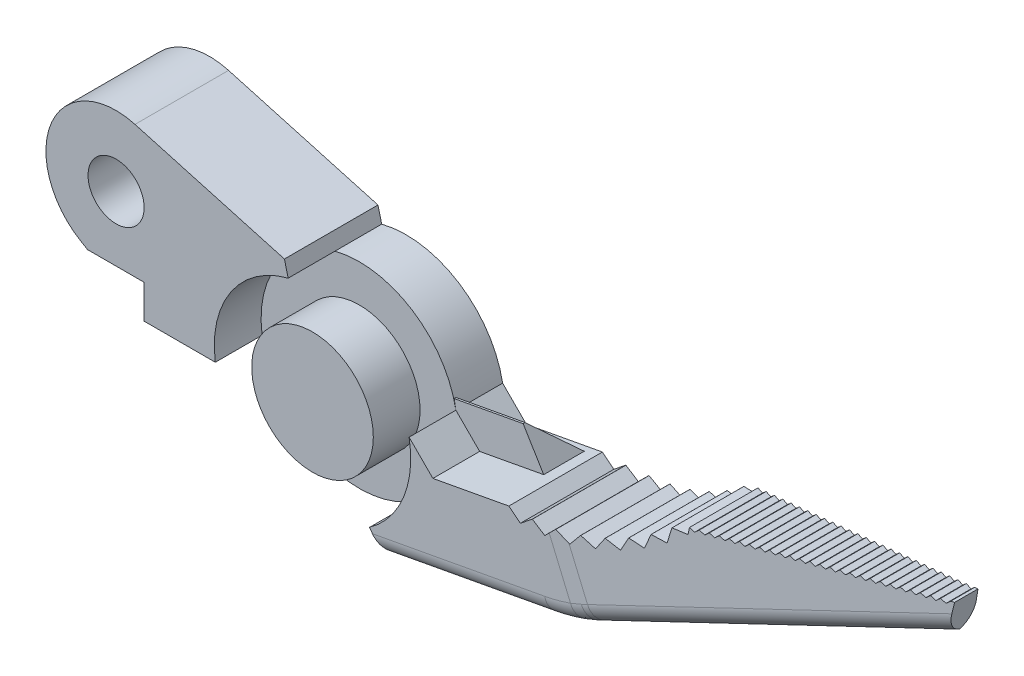
SolidWorks part; units mm, degrees
ref_plane "Front Plane" through (0, 0, 0) normal (0, 0, 1) x (1, 0, 0)
ref_plane "Top Plane" through (0, 0, 0) normal (0, 1, 0) x (1, 0, 0)
ref_plane "Right Plane" through (0, 0, 0) normal (1, 0, 0) x (0, 0, -1)
sketch "Sketch1" plane through (0, 0, 0) normal (0, 0, 1) x (1, 0, 0)
  line L0 (0, 0) -> (38.4509, 0) construction
  line L1 (0, 0) -> (32.4474, 6.0138) construction
  line L2 (-9.4882, 8.1109) -> (1.4165, 5.0553)
  line L3 (-12.417, 1.277) -> (-2.6838, -4.5122)
  line L4 (0, 0) -> (32.4474, 6.0138)
  line L5 (32.4474, 6.0138) -> (32.0857, 4.2505)
  line L6 (32.0857, 4.2505) -> (13.677, -3.5673)
  line L7 (13.677, -3.5673) -> (3.8444, -5.3897)
  line L8 (3.8444, -5.3897) -> (0, 0)
  circle A0 centre (0, 0) radius 5.25
  circle A1 centre (-10.5, 4.5) radius 3.75
  dimension "D1" = 10.5
  dimension "D2" = 7.5
  dimension "D3" = 10.5
  dimension "D4" = 4.5
  dimension "D5" = 33
  dimension "D6" = 10.5
  dimension "D7" = 65
  dimension "D8" = 10
  dimension "D9" = 6
  dimension "D10" = 20
  dimension "D11" = 1.8
extrude "Boss-Extrude1" add sketch "Sketch1" along normal mid plane 5 contours A1 | A1 L3 A0 L2 | L4 A0 L8 | L8 A0 L4 | A0 L8 L7 L6 L5 L4 region at (-5.8996, 2.5284, 0) region at (-10.5, 4.5, 0) region at (-0.6773, 0.2736, 0) region at (3.0739, -1.2419, 0) region at (15.8799, 0.3406, 0)
sketch "Sketch2" plane through (0, 0, 2.5) normal (0, 0, 1) x (1, 0, 0)
  line L0 (-12.0263, 1.0446) -> (-9, 1.0446)
  line L1 (-12.417, 1.277) -> (-2.6838, -4.5122) construction
  line L2 (-9, 1.0446) -> (-9, -0.7554)
  line L3 (-9, -0.7554) -> (-5.1954, -0.7554)
  line L4 (-12.0263, 1.0446) -> (-2.6838, -4.5122)
  arc A0 (-5.1954, -0.7554) -> (-2.6838, -4.5122) centre (0, 0) ccw
  point P6 (-18.6598, 7.6557)
  line M13 (-12.417, 1.277) -> (-2.6838, -4.5122)
  dimension "D2" = 10.5
  dimension "D1" = 1.8
  dimension "D3" = 9
extrude "Cut-Extrude1" cut sketch "Sketch2" against normal through all and the other way through all contours L2 L0 M13 | A0 L3 M13 region at (-6.0482, -1.8017, 2.5) region at (-10.0088, 0.4446, 2.5)
sketch "Sketch3" plane through (3.3732, -7.9431, 0) normal (0.3909, -0.9204, 0) x (0.9204, 0.3909, 0)
  line L0 (0, 0) -> (32.2165, 0) construction
  line L1 (32.2165, 2.5) -> (32.2165, -2.5) construction
  line L2 (12.2165, 2.5) -> (32.2165, 2.5)
  line L3 (31.1944, 2.5) -> (11.1944, 2.5) construction
  line L4 (32.2165, 2.5) -> (32.2165, 0.625)
  line L5 (32.2165, 0.625) -> (12.2165, 2.5)
  line L6 (32.2165, -2.5) -> (32.2165, -0.625)
  line L7 (12.2165, -2.5) -> (32.2165, -2.5)
  line L8 (32.2165, -0.625) -> (12.2165, -2.5)
  dimension "D1" = 1.25
  dimension "D2" = 20
extrude "Cut-Extrude2" cut sketch "Sketch3" against normal through all
fillet "Fillet1" radius 10 3 edges at (13.4609, -0.4437, -2.5) (13.4609, -0.4437, 2.5) (13.677, -3.5673, 0)
fillet "Fillet2" radius 1 10 edges at (8.2218, -4.5784, 2.5) (13.3992, -3.5845, 2.5) (14.8663, -3.0622, 2.4728) (23.5661, 0.6324, 1.5886) (8.2218, -4.5784, -2.5) (13.3992, -3.5845, -2.5) (14.8663, -3.0622, -2.4728) (23.5661, 0.6324, -1.5886)
sketch "Sketch4" plane through (0, 0, 2.5) normal (0, 0, 1) x (1, 0, 0)
  line L0 (5.1621, 0.9567) -> (6.4349, -0.3161)
  line L1 (6.4349, -0.3161) -> (10.4957, 0.4366)
  line L2 (32.4474, 6.0138) -> (12.7731, 2.3674) construction
  line L4 (5.1621, 0.9567) -> (11.833, 2.1931) construction
  line L6 (5.1621, 0.9567) -> (19, 3.5214)
  arc A0 (10.4957, 0.4366) -> (19, 3.5214) centre (10.9577, 12.4277) ccw
  dimension "D4" = 12
  dimension "D1" = 1.8
  dimension "D2" = 1.4834
  dimension "D3" = 4.13
  dimension "D5" = 19
extrude "Cut-Extrude3" cut sketch "Sketch4" against normal through all
sketch "Sketch6" plane through (0, 0, 0) normal (0, 0, 1) x (1, 0, 0)
  line L0 (32.2508, 5.9773) -> (32.0323, 5.7843)
  line L1 (32.4474, 6.0138) -> (19, 3.5214) construction
  line L2 (32.0323, 5.7843) -> (31.7591, 5.8862)
  line L3 (31.7591, 5.8862) -> (32.2508, 5.9773)
  line L4 (32.0323, 5.7843) -> (32.0049, 5.9318) construction
  point P4 (0, 0)
  point P8 (29.8103, 5.6777)
  dimension "D1" = 0.5
  dimension "D2" = 0.15
  dimension "D3" = 0.2
extrude "Cut-Extrude4" cut sketch "Sketch6" against normal mid plane 5
pattern_linear "LPattern1" count 28 spacing 0.5 along (-0.9833, -0.1822, 0) of "Cut-Extrude4"
sketch "Sketch7" plane through (0, 0, 2.5) normal (0, 0, 1) x (1, 0, 0)
  circle A0 centre (0, 0) radius 5.25
  dimension "D1" = 10.5
extrude "Cut-Extrude5" cut sketch "Sketch7" against normal blind 2.5
sketch "Sketch8" plane through (0, 0, 2.5) normal (0, 0, 1) x (1, 0, 0)
  line L0 (10.4957, 0.4366) -> (11.7457, 0.4536)
  line L1 (11.7457, 0.4536) -> (11.1101, -0.0551)
  line L2 (11.1101, -0.0551) -> (10.4957, 0.4366)
  line L3 (11.1101, -0.0551) -> (11.1101, 0.4449) construction
  arc A0 (10.4957, 0.4366) -> (12.5383, 0.5322) centre (10.9577, 12.4277) ccw construction
  dimension "D1" = 1.25
  dimension "D2" = 0.5
extrude "Cut-Extrude6" cut sketch "Sketch8" against normal through all
pattern_circular "CirPattern1" count 8 every 6 about axis through (10.9577, 12.4277, -2.5244) along (0, 0, 1) of "Cut-Extrude6"
ref_plane "Plane1" through (5.1621, 0.9567, 0) normal (0.9833, 0.1822, 0) x (0, 0, -1)
sketch "Sketch9" plane through (5.1621, 0.9567, 0) normal (0.9833, 0.1822, 0) x (0, 0, -1)
  line L0 (0.1, 0.5) -> (0, 0.5)
  line L1 (0, 3.5184) -> (0, -3.9475) construction
  line L2 (0, 0.5) -> (0, -1.8)
  line L3 (0, 5.25) -> (0, -5.25) construction
  line L4 (0, -1.8) -> (2.5, -1.8)
  line L5 (2.5, -2.0456) -> (2.5, -4.8877) construction
  line L6 (2.5, -1.8) -> (0.1, 0.5)
  dimension "D1" = 0.1
  dimension "D2" = 0.5
  dimension "D3" = 2.3
extrude "Boss-Extrude2" add sketch "Sketch9" along normal blind 4.5
sketch "Sketch10" plane through (0, 0, 0) normal (0, 0, 1) x (1, 0, 0)
  line L0 (8.7582, 2.1317) -> (9.4956, 2.2684)
  line L1 (9.4956, 2.2684) -> (5.071, 1.4484) construction
  line L2 (9.4956, 2.2684) -> (9.8571, 0.3182)
  line L3 (9.8571, 0.3182) -> (8.7582, 2.1317)
  dimension "D1" = 0.75
extrude "Cut-Extrude7" cut sketch "Sketch10" against normal blind 4.5
sketch "Sketch11" plane through (0, 0, 2.5) normal (0, 0, 1) x (1, 0, 0)
  circle A0 centre (-10.5, 4.5) radius 1.5
  dimension "D1" = 3
extrude "Cut-Extrude8" cut sketch "Sketch11" against normal through all
sketch "Sketch12" plane through (0, -0.7554, 0) normal (0, -1, 0) x (1, 0, 0)
  line L0 (-9, -2.5) -> (-5.1954, 2.5) construction
  circle A0 centre (-7.0977, 0) radius 1.25
  dimension "D1" = 2.5
extrude "Cut-Extrude9" cut sketch "Sketch12" against normal blind 2
sketch "Sketch13" plane through (0, 0, 2.5) normal (0, 0, 1) x (1, 0, 0)
  line L0 (0, 0) -> (1.4165, 5.0553)
  line L1 (1.4165, 5.0553) -> (-1.5021, 5.8731)
  line L2 (-9.4882, 8.1109) -> (1.4165, 5.0553) construction
  line L3 (-1.5021, 5.8731) -> (0, 0)
  arc A0 (1.4165, 5.0553) -> (-5.1954, -0.7554) centre (0, 0) ccw construction
  arc A1 (1.4165, 5.0553) -> (-5.1954, -0.7554) centre (0, 0) ccw
  arc M4 (-5.1954, -0.7554) -> (1.4165, 5.0553) centre (0, 0) cw
  line M5 (1.4165, 5.0553) -> (-9.4882, 8.1109)
  dimension "D1" = 30
extrude "Cut-Extrude10" cut sketch "Sketch13" against normal through all contours L3 M5 M4 region at (-0.6908, 5.4242, 2.5)
sketch "Sketch14" plane through (0, 0, 0) normal (0, 0, 1) x (1, 0, 0)
  circle A0 centre (0, 0) radius 3.25
  dimension "D1" = 6.5
extrude "Boss-Extrude3" add sketch "Sketch14" along normal blind 2.5
